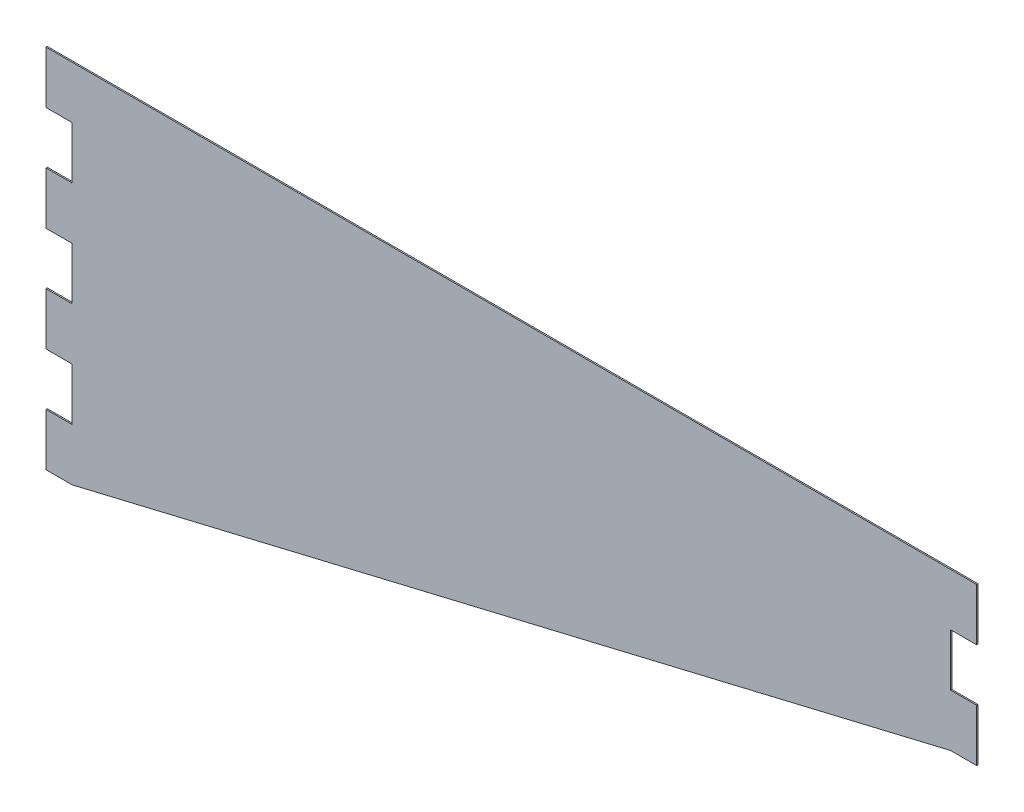
SolidWorks part; units mm, degrees
ref_plane "Front Plane" through (0, 0, 0) normal (0, 0, 1) x (1, 0, 0)
ref_plane "Top Plane" through (0, 0, 0) normal (0, 1, 0) x (1, 0, 0)
ref_plane "Right Plane" through (0, 0, 0) normal (1, 0, 0) x (0, 0, -1)
sketch "Sketch2" plane through (0, 0, 0) normal (0, 0, 1) x (1, 0, 0)
  line L0 (0, 0) -> (5, 0)
  line L1 (5, 0) -> (173, 40)
  line L2 (173, 40) -> (178, 40)
  line L3 (178, 40) -> (178, 70)
  line L4 (178, 70) -> (0, 70)
  line L5 (0, 70) -> (0, 0)
  dimension "D1" = 70
  dimension "D2" = 5
  dimension "D3" = 5
  dimension "D4" = 168
  dimension "D5" = 30
extrude "Boss-Extrude1" add sketch "Sketch2" along normal mid plane 0.25
sketch "Sketch3" plane through (0, 0, 0.125) normal (0, 0, 1) x (1, 0, 0)
  line L1 (0, 60) -> (5, 60)
  line L2 (0, 60) -> (0, 50)
  line L3 (0, 50) -> (5, 50)
  line L4 (5, 60) -> (5, 50)
  line L5 (178, 70) -> (0, 70) construction
  dimension "D1" = 5
  dimension "D2" = 10
  dimension "D3" = 10
extrude "Cut-Extrude1" cut sketch "Sketch3" against normal through all
pattern_linear "LPattern2" count 4 spacing 20 along (0, -1, 0) count 2 spacing 173 along (1, 0, 0) of "Cut-Extrude1"
